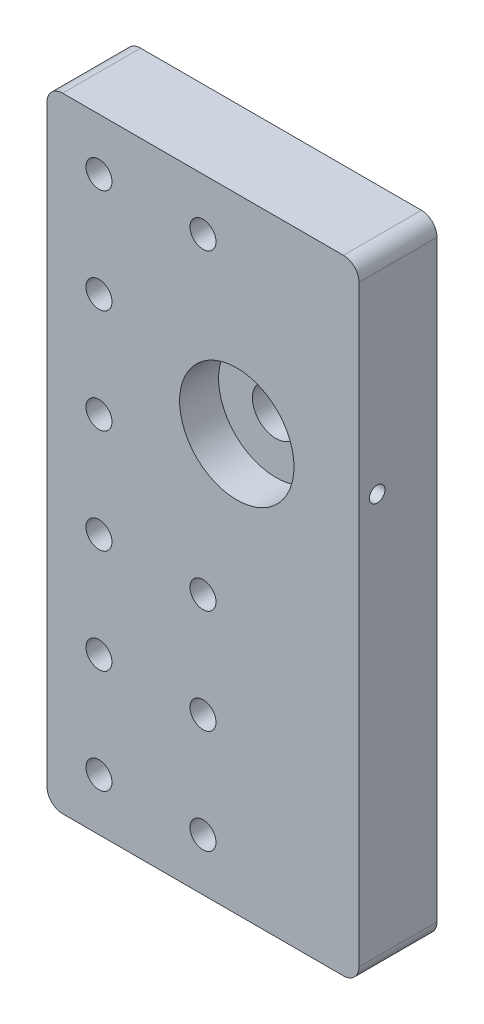
SolidWorks part; units mm, degrees
ref_plane "Płaszczyzna przednia" through (0, 0, 0) normal (0, 0, 1) x (1, 0, 0)
ref_plane "Płaszczyzna górna" through (0, 0, 0) normal (0, 1, 0) x (1, 0, 0)
ref_plane "Płaszczyzna prawa" through (0, 0, 0) normal (1, 0, 0) x (0, 0, -1)
sketch "Sketch1" plane through (0, 0, 0) normal (0, 0, 1) x (1, 0, 0)
  line L0 (72.0964, 110) -> (-17.7275, 110) construction
  line L1 (0, 0) -> (60, 0)
  line L2 (0, 0) -> (0, 120)
  line L3 (0, 120) -> (60, 120)
  line L4 (60, 0) -> (60, 120)
  line L5 (10, 111.3456) -> (10, -27.1164) construction
  line L6 (-17.7275, 10) -> (75.4304, 10) construction
  line L7 (-17.7275, 50) -> (77.7275, 50) construction
  circle A0 centre (10, 110) radius 2.5
  circle A1 centre (30, 110) radius 2.5
  circle A2 centre (10, 90) radius 2.5
  circle A3 centre (10, 70) radius 2.5
  circle A5 centre (10, 10) radius 2.5
  circle A6 centre (30, 10) radius 2.5
  circle A8 centre (30, 50) radius 2.5
  circle A9 centre (10, 50) radius 2.5
  circle A10 centre (10, 30) radius 2.5
  circle A11 centre (30, 30) radius 2.5
  dimension "D11" = 5
  dimension "D1" = 120
  dimension "D2" = 60
  dimension "D3" = 10
  dimension "D4" = 10
  dimension "D5" = 10
  dimension "D6" = 20
  dimension "D7" = 20
  dimension "D8" = 20
  dimension "D9" = 20
  dimension "D10" = 20
  dimension "D12" = 20
extrude "Boss-Extrude1" add sketch "Sketch1" along normal blind 15
fillet "Fillet1" radius 3 4 edges at (0, 0, 7.5) (60, 0, 7.5) (0, 120, 7.5) (60, 120, 7.5)
sketch "Sketch2" plane through (0, 0, 15) normal (0, 0, 1) x (1, 0, 0)
  line L0 (45.9963, 120) -> (36.5, 120) construction
  line L1 (57, 120) -> (3, 120) construction
  line L2 (36.5, 120) -> (36.5, 0) construction
  line L3 (3, 0) -> (57, 0) construction
  line L4 (0, 117) -> (0, 3) construction
  line L5 (0, 80) -> (60, 80) construction
  line L6 (60, 3) -> (60, 117) construction
  circle A0 centre (10, 70) radius 2.5 construction
  circle A1 centre (10, 90) radius 2.5 construction
  circle A2 centre (36.5, 80) radius 11
  circle A7 centre (36.5, 80) radius 4.5
  dimension "D5" = 22
  dimension "D6" = 9
  dimension "D1" = 36.5
extrude "Cut-Extrude1" cut sketch "Sketch2" against normal through all contours A7
extrude "Cut-Extrude2" cut sketch "Sketch2<3>" against normal blind 7.5 contours A2 A7 region at (25.8111, 80, 15)
sketch "Sketch2<3>" plane through (0, 0, 15) normal (0, 0, 1) x (1, 0, 0) same geometry as "Sketch2"
sketch "Sketch3" plane through (60, 0, 0) normal (1, 0, 0) x (0, 0, -1)
  line L1 (-15, 3) -> (-15, 117) construction
  line L2 (-15, 91) -> (-15, 69) construction
  circle A0 centre (-11.5, 80) radius 1.5
  point P2 (0, 0)
  point P4 (-15, 80)
  dimension "D1" = 3
  dimension "D2" = 3.5
extrude "Cut-Extrude3" cut sketch "Sketch3" against normal up to next
